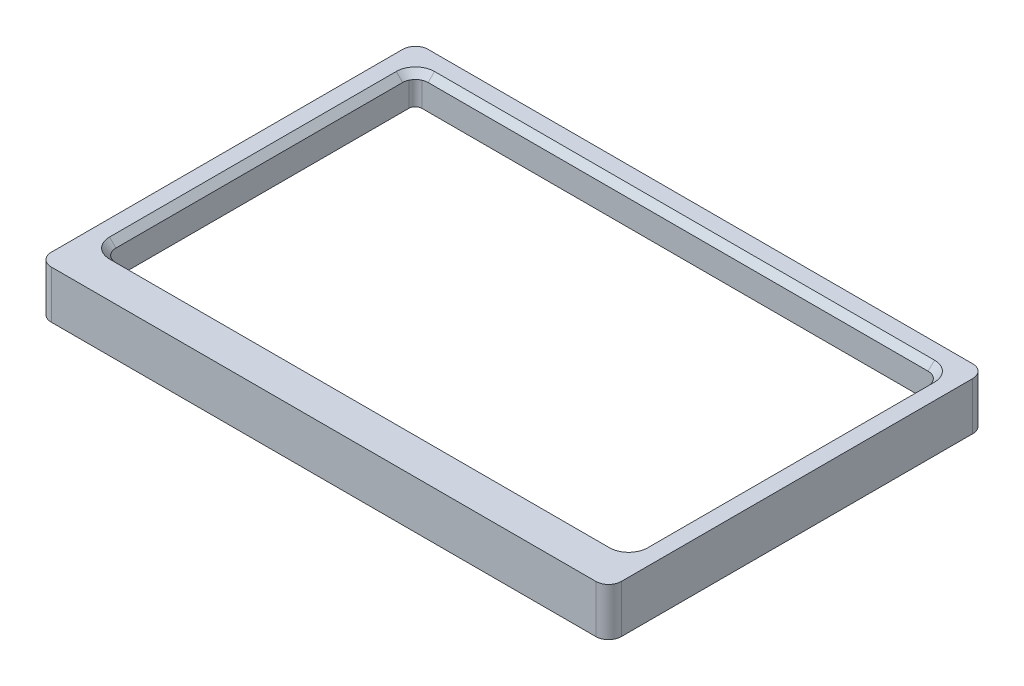
SolidWorks part; units mm, degrees
ref_plane "前基準面" through (0, 0, 0) normal (0, 0, 1) x (1, 0, 0)
ref_plane "上基準面" through (0, 0, 0) normal (0, 1, 0) x (1, 0, 0)
ref_plane "右基準面" through (0, 0, 0) normal (1, 0, 0) x (0, 0, -1)
sketch "草圖1" plane through (0, 0, 0) normal (0, 1, 0) x (1, 0, 0)
  line L1 (-89.4, 59.1) -> (89.4, 59.1)
  line L2 (-89.4, 59.1) -> (-89.4, -59.1)
  line L3 (-89.4, -59.1) -> (89.4, -59.1)
  line L4 (89.4, 59.1) -> (89.4, -59.1)
  line L5 (-89.4, 59.1) -> (89.4, -59.1) construction
  line L6 (-89.4, -59.1) -> (89.4, 59.1) construction
  point P0 (0, 0)
  dimension "D1" = 118.2
  dimension "D2" = 178.8
extrude "填料-伸長1" add sketch "草圖1" along normal blind 15
fillet "圓角1" radius 4 4 edges at (89.4, 7.5, -59.1) (89.4, 7.5, 59.1) (-89.4, 7.5, 59.1) (-89.4, 7.5, -59.1)
shell "薄殼1" thickness 2 removed face at (0, 0, 0)
sketch "草圖2" plane through (0, 15, 0) normal (0, 1, 0) x (1, 0, 0)
  line L0 (85.4, 59.1) -> (-85.4, 59.1) construction
  line L1 (-82.4, 52.1) -> (82.4, 52.1)
  line L2 (-82.4, 52.1) -> (-82.4, -45.82)
  line L3 (-82.4, -45.82) -> (82.4, -45.82)
  line L4 (82.4, 52.1) -> (82.4, -45.82)
  line L5 (-82.4, 52.1) -> (82.4, -45.82) construction
  line L6 (-82.4, -45.82) -> (82.4, 52.1) construction
  line L7 (0, 59.1) -> (0, -59.1) construction
  line L8 (-85.4, -59.1) -> (85.4, -59.1) construction
  point P0 (0, 3.14)
  point P5 (0, 0)
  point P8 (0, 3.14)
  dimension "D1" = 7
  dimension "D2" = 164.8
  dimension "D3" = 97.92
extrude "除料-伸長1" cut sketch "草圖2" against normal up to surface (2 mm away) up to face at (0, 13, 0)
fillet "圓角2" radius 4 4 edges at (82.4, 14, -52.1) (82.4, 14, 45.82) (-82.4, 14, 45.82) (-82.4, 14, -52.1)
chamfer "導角1" distance 2 angle 45 8 edges at (0, 15, 45.82) (81.2284, 15, 44.6484) (-81.2284, 15, 44.6484) (82.4, 15, -3.14) (-82.4, 15, -3.14) (81.2284, 15, -50.9284) (-81.2284, 15, -50.9284) (0, 15, -52.1)
